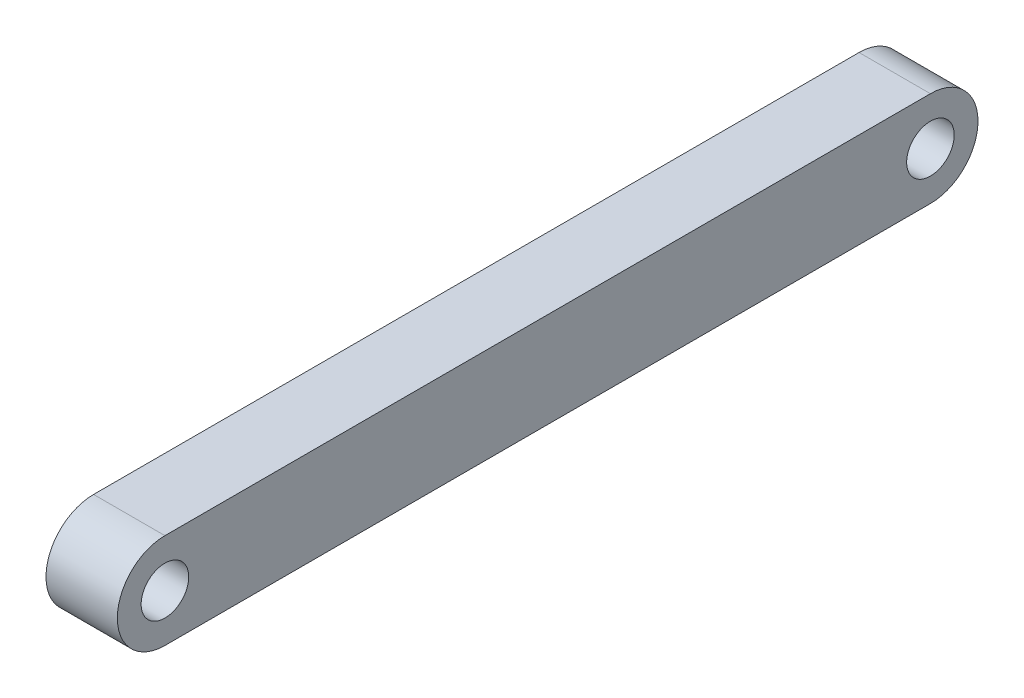
SolidWorks part; units mm, degrees
ref_plane "Front Plane" through (0, 0, 0) normal (0, 0, 1) x (1, 0, 0)
ref_plane "Top Plane" through (0, 0, 0) normal (0, 1, 0) x (1, 0, 0)
ref_plane "Right Plane" through (0, 0, 0) normal (1, 0, 0) x (0, 0, -1)
sketch "Sketch1" plane through (0, 0, 0) normal (1, 0, 0) x (0, 0, -1)
  line L4 (-16.09, -2) -> (16.09, -2)
  line L6 (-16.09, 2) -> (16.09, 2)
  line L8 (-16.09, -2) -> (16.09, 2) construction
  line L9 (-16.09, 2) -> (16.09, -2) construction
  arc A4 (16.09, 2) -> (16.09, -2) centre (16.09, 0) cw
  arc A5 (-16.09, 2) -> (-16.09, -2) centre (-16.09, 0) ccw
  circle A6 centre (-16.09, 0) radius 1
  circle A7 centre (16.09, 0) radius 1
  point P0 (0, 0)
  point P1 (0, 0)
  dimension "D2" = 4
  dimension "D3" = 2
  dimension "D1" = 32.18
extrude "Boss-Extrude1" add sketch "Sketch1" along normal mid plane 3
